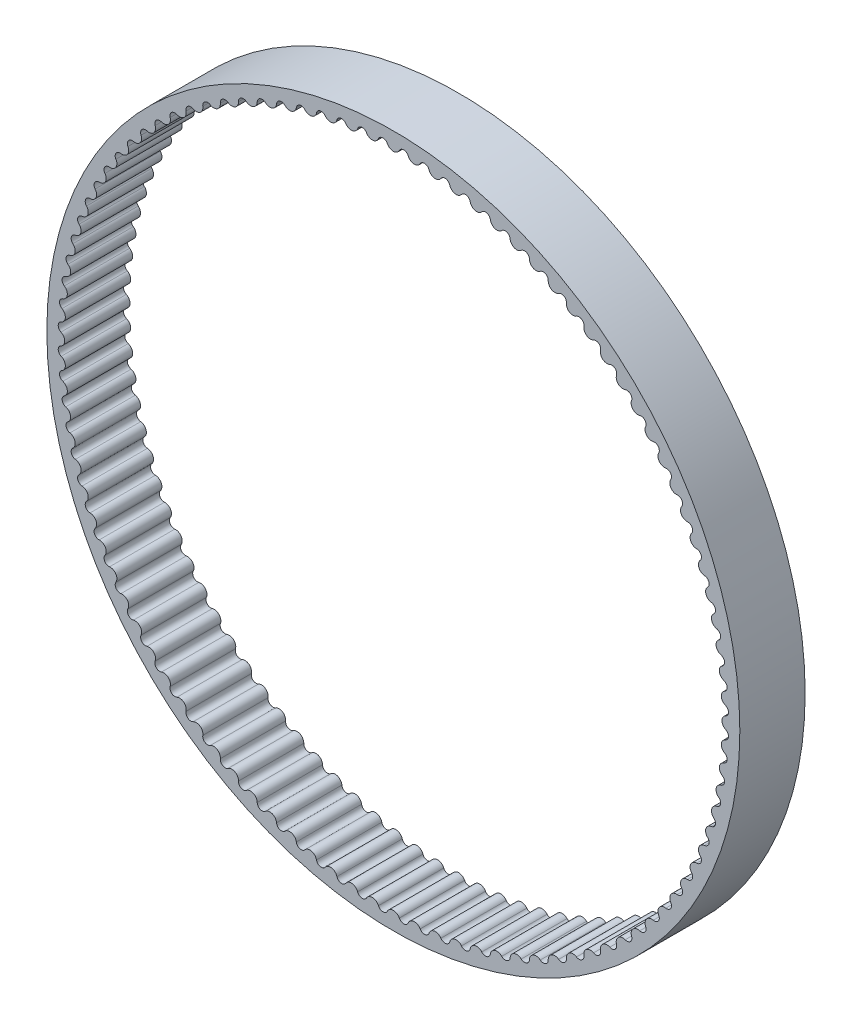
SolidWorks part; units mm, degrees
ref_plane "Front Plane" through (0, 0, 0) normal (0, 0, 1) x (1, 0, 0)
ref_plane "Top Plane" through (0, 0, 0) normal (0, 1, 0) x (1, 0, 0)
ref_plane "Right Plane" through (0, 0, 0) normal (1, 0, 0) x (0, 0, -1)
sketch "Sketch1" plane through (0, 0, 0) normal (0, 0, 1) x (1, 0, 0)
  line L0 (0, 0) -> (0, 30.801) construction
  line L1 (0, 0) -> (1.934, 30.7402) construction
  line L2 (0, 0) -> (3.8604, 30.5581) construction
  line L3 (-1.934, 30.7402) -> (0, 0) construction
  circle A0 centre (0, 0) radius 31.831
  circle A1 centre (0, 0) radius 30.191
  circle A2 centre (0, 0) radius 30.801 construction
  circle A10 centre (0, 30.801) radius 0.61
  circle A101 centre (1.934, 30.7402) radius 0.61
  circle A102 centre (0.9533, 30.3349) radius 0.4512
  circle A103 centre (-0.9533, 30.3349) radius 0.4512
  circle A104 centre (-1.934, 30.7402) radius 0.61
  point P16 (-1.8957, 30.1314)
  point P17 (0, 30.191)
  point P77 (0, 0)
  dimension "OD" = 63.662
  dimension "Tooth Diameter" = 1.22
  dimension "Belt Thickness" = 1.64
  dimension "Angle" = 3.6
  dimension "D3" = 3.6
sketch "Sketch2" plane through (0, 0, 0) normal (0, 0, 1) x (1, 0, 0)
  circle A0 centre (0, 0) radius 30.191 construction
  circle A1 centre (0, 0) radius 31.831 construction
  circle A2 centre (0, 0) radius 30.191
  circle A3 centre (0, 0) radius 31.831
extrude "Boss-Extrude1" add sketch "Sketch2" along normal mid plane 6
sketch "Sketch3" plane through (0, 0, 0) normal (0, 0, 1) x (1, 0, 0)
  circle A0 centre (0, 0) radius 30.191 construction
  circle A1 centre (1.934, 30.7402) radius 0.61 construction
  circle A2 centre (0.9533, 30.3349) radius 0.4512 construction
  circle A3 centre (0, 30.801) radius 0.61 construction
  arc A4 (1.8957, 30.1314) -> (0, 30.191) centre (0, 0) ccw
  arc A5 (1.3703, 30.5072) -> (1.8957, 30.1314) centre (1.934, 30.7402) ccw
  arc A6 (1.3703, 30.5072) -> (0.548, 30.5331) centre (0.9533, 30.3349) ccw
  arc A7 (0, 30.191) -> (0.548, 30.5331) centre (0, 30.801) ccw
extrude "Cut-Extrude1" cut sketch "Sketch3" against normal through all both and the other way through all
pattern_circular "CirPattern3" count 100 over 360 about axis through (0, 0, 3) along (0, 0, -1) of "Cut-Extrude1"
ref_axis "Center Axis 1" through (0, 0, 3) along (0, 0, -1)
equation "\"D3@Sketch1\" = \"Angle@Sketch1\""
